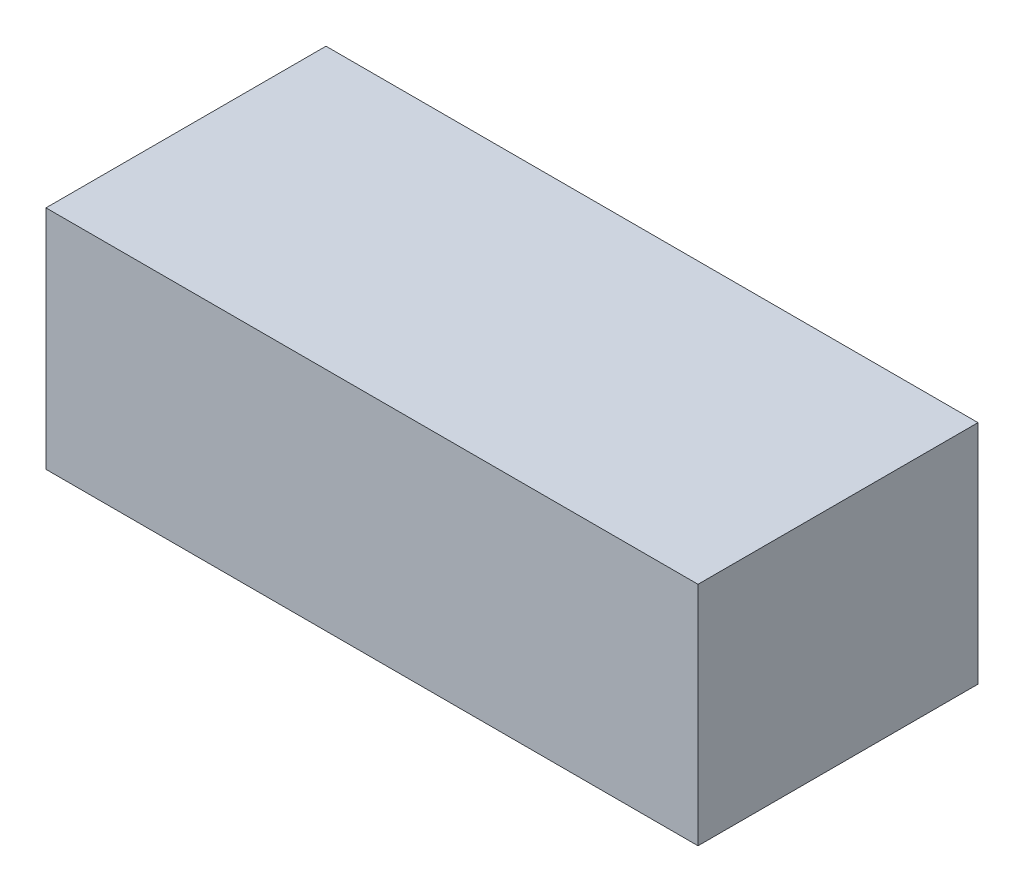
SolidWorks part; units mm, degrees
ref_plane "XY" through (0, 0, 0) normal (0, 0, 1) x (1, 0, 0)
ref_plane "XZ" through (0, 0, 0) normal (0, 1, 0) x (1, 0, 0)
ref_plane "YZ" through (0, 0, 0) normal (1, 0, 0) x (0, 0, -1)
ref_axis "X" through (-88.99, 0, 0) along (1, 0, 0)
ref_axis "Y" through (0, -55, 0) along (0, 1, 0)
ref_axis "Z" through (0, 0, 55) along (0, 0, -1)
sketch "Sketch1" plane through (0, 0, 0) normal (0, 1, 0) x (1, 0, 0)
  line L1 (-21.59, -9.271) -> (21.59, -9.271)
  line L2 (-21.59, -9.271) -> (-21.59, 9.271)
  line L3 (-21.59, 9.271) -> (21.59, 9.271)
  line L4 (21.59, -9.271) -> (21.59, 9.271)
  line L5 (-21.59, -9.271) -> (21.59, 9.271) construction
  line L6 (-21.59, 9.271) -> (21.59, -9.271) construction
  point P0 (0, 0)
  dimension "D1" = 43.18
  dimension "D2" = 18.542
extrude "Boss-Extrude1" add sketch "Sketch1" along normal blind 15
